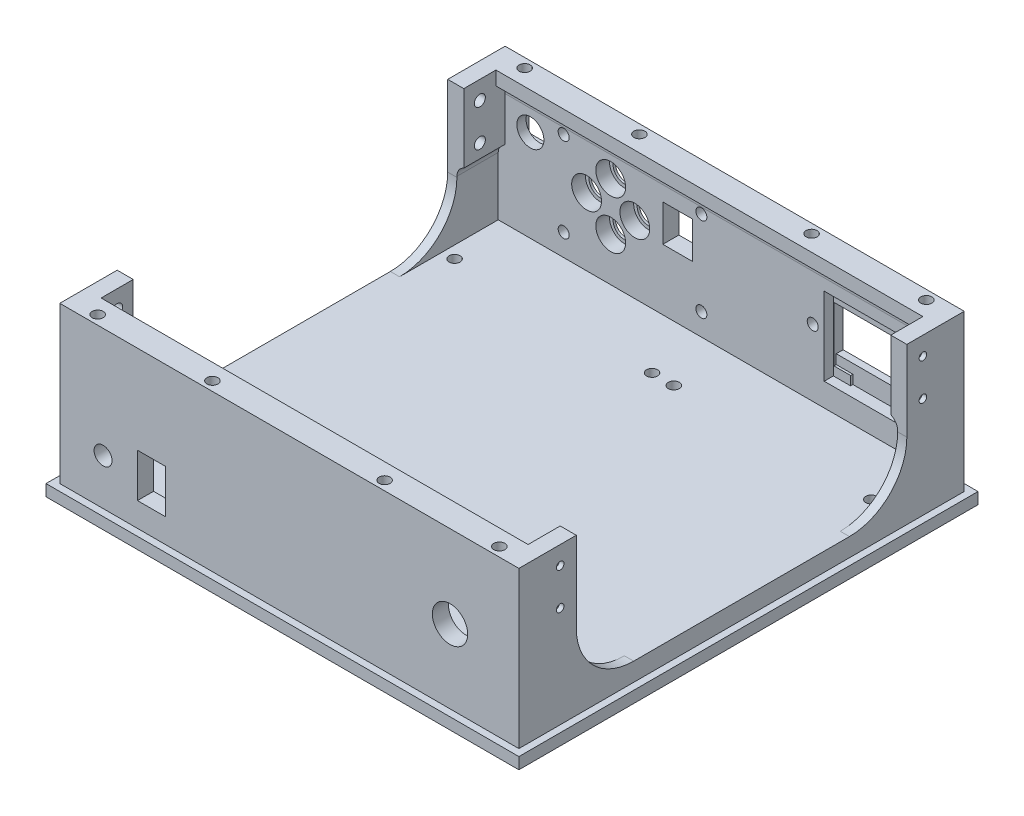
SolidWorks part; units mm, degrees
ref_plane "Front Plane" through (0, 0, 0) normal (0, 0, 1) x (1, 0, 0)
ref_plane "Top Plane" through (0, 0, 0) normal (0, 1, 0) x (1, 0, 0)
ref_plane "Right Plane" through (0, 0, 0) normal (1, 0, 0) x (0, 0, -1)
sketch "Sketch1" plane through (0, 0, 0) normal (0, 1, 0) x (1, 0, 0)
  line L1 (0, 0) -> (200, 0)
  line L2 (0, 0) -> (0, -194)
  line L3 (0, -194) -> (200, -194)
  line L4 (200, 0) -> (200, -194)
  dimension "D1" = 194
  dimension "D2" = 200
extrude "Boss-Extrude1" add sketch "Sketch1" along normal blind 8
sketch "Sketch4" plane through (0, 8, 0) normal (0, 1, 0) x (1, 0, 0)
  line L0 (0, -97) -> (200, -97) construction
  line L1 (0, 0) -> (0, -194) construction
  line L2 (200, -194) -> (200, 0) construction
  line L3 (100, 0) -> (100, -194) construction
  line L4 (200, 0) -> (0, 0) construction
  line L5 (0, -194) -> (200, -194) construction
  line L7 (9.25, -31.25) -> (95.25, -31.25) construction
  line L8 (9.25, -162.75) -> (95.25, -162.75) construction
  line L11 (190.75, -162.75) -> (104.75, -162.75) construction
  line L12 (190.75, -31.25) -> (104.75, -31.25) construction
  circle A0 centre (9.25, -31.25) radius 1.5 construction
  circle A1 centre (9.25, -31.25) radius 2.4
  circle A2 centre (95.25, -31.25) radius 1.5 construction
  circle A3 centre (95.25, -31.25) radius 2.4
  circle A4 centre (95.25, -162.75) radius 2.4
  circle A5 centre (95.25, -162.75) radius 1.5 construction
  circle A6 centre (9.25, -162.75) radius 2.4
  circle A7 centre (9.25, -162.75) radius 1.5 construction
  circle A8 centre (190.75, -162.75) radius 1.5 construction
  circle A9 centre (190.75, -162.75) radius 2.4
  circle A10 centre (104.75, -162.75) radius 1.5 construction
  circle A11 centre (104.75, -162.75) radius 2.4
  circle A12 centre (104.75, -31.25) radius 2.4
  circle A13 centre (104.75, -31.25) radius 1.5 construction
  circle A14 centre (190.75, -31.25) radius 2.4
  circle A15 centre (190.75, -31.25) radius 1.5 construction
  point P16 (9.25, -29.75)
  point P20 (7.75, -31.25)
  point P21 (96.75, -31.25)
  point P29 (96.75, -162.75)
  point P30 (7.75, -162.75)
  point P31 (9.25, -164.25)
  point P46 (190.75, -164.25)
  point P47 (192.25, -162.75)
  point P48 (103.25, -162.75)
  point P49 (103.25, -31.25)
  point P50 (192.25, -31.25)
  point P51 (190.75, -29.75)
  dimension "D1" = 3
  dimension "D2" = 4.8
  dimension "D4" = 3
  dimension "D5" = 4.8
  dimension "D3" = 67.25
  dimension "D6" = 89
  dimension "D7" = 4.75
  dimension "D8" = 9.5
  dimension "D9" = 134.5
  dimension "D10" = 184.5
extrude "Cut-Extrude1" cut sketch "Sketch4" against normal blind 6
sketch "Sketch5" plane through (0, 8, 0) normal (0, 1, 0) x (1, 0, 0)
  line L1 (0, 0) -> (200, 0)
  line L2 (0, 0) -> (0, -194)
  line L3 (0, -194) -> (200, -194)
  line L4 (200, 0) -> (200, -194)
  line L5 (196, -7) -> (196, -187)
  line L7 (4, -7) -> (4, -187)
  line L8 (196, -4) -> (196, -190) construction
  line L9 (4, -7) -> (196, -7)
  line L10 (4, -4) -> (4, -190) construction
  line L11 (4, -4) -> (196, -4) construction
  line L12 (0, -194) -> (0, -187) construction
  line L13 (4, -187) -> (196, -187)
  line L15 (4, -190) -> (196, -190) construction
  dimension "D1" = 4
  dimension "D2" = 7
extrude "Boss-Extrude4" add sketch "Sketch5" along normal blind 60
sketch "Sketch6" plane through (0, 0, 7) normal (0, 0, 1) x (1, 0, 0)
  line L7 (196, 68) -> (4, 68)
  line L8 (0, 68) -> (200, 68) construction
  line L9 (4, 68) -> (4, 62)
  line L11 (196, 62) -> (196, 68)
  line L12 (4, 62) -> (196, 62) construction
  line L13 (4, 62) -> (196, 62)
  dimension "D1" = 6
extrude "Boss-Extrude5" add sketch "Sketch6" along normal blind 4
sketch "Sketch7" plane through (0, 68, 0) normal (0, 1, 0) x (1, 0, 0)
  line L0 (0, 0) -> (0, -8) construction
  line L1 (0, 0) -> (0, -194) construction
  line L2 (0, -8) -> (200, -8) construction
  line L4 (200, -8) -> (200, 0) construction
  line L5 (200, 0) -> (0, 0) construction
  line L6 (0, -4) -> (200, -4) construction
  circle A0 centre (12.5, -4) radius 2.4
  circle A1 centre (62.5, -4) radius 2.4
  circle A2 centre (187.5, -4) radius 2.4
  circle A3 centre (137.5, -4) radius 2.4
  dimension "D2" = 4.8
  dimension "D3" = 4.8
  dimension "D4" = 4.8
  dimension "D5" = 4.8
  dimension "D1" = 8
  dimension "D6" = 12.5
  dimension "D7" = 50
  dimension "D8" = 12.5
  dimension "D9" = 50
extrude "Cut-Extrude2" cut sketch "Sketch7" against normal blind 6
ref_plane "Plane1" through (0, 0, 97) normal (0, 0, 1) x (1, 0, 0)
mirror "Mirror3" about plane through (0, 0, 97) normal (0, 0, 1) of "Boss-Extrude5"
mirror "Mirror5" about plane through (0, 0, 97) normal (0, 0, 1) of "Cut-Extrude2"
sketch "Sketch10" plane through (0, 0, 194) normal (0, 0, 1) x (1, 0, 0)
  line L0 (0, 68) -> (40, 68) construction
  line L1 (0, 68) -> (200, 68) construction
  line L2 (33.85, 20) -> (18.85, 20) construction
  line L3 (170, 0) -> (200, 0) construction
  line L4 (170, 32) -> (170, 0) construction
  line L5 (33.85, 29.5) -> (46.15, 29.5)
  line L6 (33.85, 29.5) -> (33.85, 10.5)
  line L7 (33.85, 10.5) -> (46.15, 10.5)
  line L8 (46.15, 29.5) -> (46.15, 10.5)
  line L9 (33.85, 29.5) -> (46.15, 10.5) construction
  line L10 (33.85, 10.5) -> (46.15, 29.5) construction
  line L11 (0, 0) -> (200, 0) construction
  line L12 (18.85, 20) -> (18.85, 0) construction
  circle A1 centre (18.85, 20) radius 3.9
  circle A3 centre (170, 32) radius 7.7
  point P8 (40, 20)
  point P22 (170, 32)
  point P24 (170, 0)
  dimension "D6" = 15.4
  dimension "7.8" = 7.8
  dimension "D8" = 32
  dimension "D1" = 40
  dimension "D2" = 19
  dimension "D3" = 12.3
  dimension "D4" = 20
  dimension "D5" = 15
  dimension "D7" = 30
extrude "Cut-Extrude4" cut sketch "Sketch10" against normal blind 10
ref_plane "Plane2" through (100, 0, 0) normal (1, 0, 0) x (0, 0, -1)
sketch "Sketch14" plane through (0, 0, 0) normal (0, 0, -1) x (-1, 0, 0)
  line L0 (0, 68) -> (-15, 68) construction
  line L1 (-200, 68) -> (0, 68) construction
  line L2 (-15, 68) -> (-15, 48) construction
  dimension "D1" = 15
  dimension "D2" = 20
sketch "Sketch16" plane through (0, 0, 0) normal (0, 0, -1) x (-1, 0, 0)
  line L0 (-75.7, 50.6) -> (-75.7, 34.6)
  line L1 (-75.7, 34.6) -> (-88.7, 34.6)
  line L2 (-88.7, 34.6) -> (-88.7, 50.6)
  line L3 (-88.7, 50.6) -> (-75.7, 50.6)
  line L4 (-75.7, 34.6) -> (-63.5, 34.6) construction
  line L5 (-63.5, 34.6) -> (-63.5, 37.5) construction
  line L6 (-63.5, 37.5) -> (-42.5, 37.5) construction
  line L7 (-53, 48) -> (-53, 27) construction
  line L8 (-18, 48) -> (-18, 37.5) construction
  line L9 (-18, 37.5) -> (-42.5, 37.5) construction
  line L11 (-18, 48) -> (0, 48) construction
  line L12 (0, 68) -> (0, 0) construction
  circle A0 centre (-53, 48) radius 5
  circle A1 centre (-63.5, 37.5) radius 5
  circle A2 centre (-42.5, 37.5) radius 5
  circle A3 centre (-53, 27) radius 5
  circle A4 centre (-18, 48) radius 5.9
  dimension "D5" = 10
  dimension "D6" = 10
  dimension "D7" = 10
  dimension "D8" = 10
  dimension "D13" = 11.8
  dimension "D1" = 12.2
  dimension "D2" = 16
  dimension "D3" = 13
  dimension "D4" = 2.9
  dimension "D9" = 21
  dimension "D10" = 21
  dimension "D11" = 24.5
  dimension "D12" = 10.5
  dimension "D14" = 14.8492
  dimension "D15" = 14.8492
  dimension "D16" = 18
extrude "Cut-Extrude5" cut sketch "Sketch16" against normal blind 10
sketch "Sketch17" plane through (0, 0, 0) normal (0, 0, -1) x (-1, 0, 0)
  line L1 (-25.5, 55.5) -> (-10.5, 55.5)
  line L2 (-25.5, 55.5) -> (-25.5, 40.5)
  line L3 (-25.5, 40.5) -> (-10.5, 40.5)
  line L4 (-10.5, 55.5) -> (-10.5, 40.5)
  line L5 (-25.5, 55.5) -> (-10.5, 40.5) construction
  line L6 (-25.5, 40.5) -> (-10.5, 55.5) construction
  point P0 (-18, 48)
  dimension "D1" = 15
extrude "Cut-Extrude6" cut sketch "Sketch17" against normal blind 3
sketch "Sketch19" plane through (0, 0, 7) normal (0, 0, 1) x (1, 0, 0)
  line L0 (32.5, 54.4) -> (92.5, 54.4) construction
  line L1 (92.5, 54.4) -> (92.5, 17.6) construction
  line L2 (92.5, 17.6) -> (32.5, 17.6) construction
  line L3 (32.5, 17.6) -> (32.5, 54.4) construction
  line L4 (42.5, 37.5) -> (32.5, 37.5) construction
  circle A0 centre (32.5, 54.4) radius 2.4
  circle A1 centre (92.5, 54.4) radius 2.4
  circle A2 centre (92.5, 17.6) radius 2.4
  circle A3 centre (32.5, 17.6) radius 2.4
  circle A6 centre (42.5, 37.5) radius 5
  circle A7 centre (42.5, 37.5) radius 5 construction
  point P12 (42.5, 37.5)
  dimension "D7" = 4.8
  dimension "D8" = 4.8
  dimension "D9" = 4.8
  dimension "D10" = 4.8
  dimension "D1" = 36.8
  dimension "D2" = 10
  dimension "D4" = 60
  dimension "D5" = 60
  dimension "D6" = 36.8
  dimension "D11" = 0
extrude "Cut-Extrude7" cut sketch "Sketch19" against normal blind 5
sketch "Sketch20" plane through (0, 0, 7) normal (0, 0, 1) x (1, 0, 0)
  circle A0 centre (53, 48) radius 6.5
  circle A1 centre (42.5, 37.5) radius 6.5
  circle A2 centre (53, 27) radius 6.5
  circle A3 centre (63.5, 37.5) radius 6.5
  dimension "D1" = 13
  dimension "D2" = 13
  dimension "D3" = 13
  dimension "D4" = 13
extrude "Cut-Extrude8" cut sketch "Sketch20" against normal blind 6
sketch "Sketch22" plane through (0, 0, 7) normal (0, 0, 1) x (1, 0, 0)
  line L0 (181, 52.101) -> (181, 62) construction
  line L2 (4, 62) -> (196, 62) construction
  line L3 (146, 52.101) -> (181, 52.101)
  line L4 (146, 18.101) -> (181, 18.101)
  line L5 (181, 18.101) -> (181, 52.101)
  line L6 (146, 52.101) -> (146, 18.101)
  line L7 (146.25, 46.001) -> (180.75, 46.001) construction
  line L8 (180.75, 46.001) -> (180.75, 26.101) construction
  line L9 (180.75, 26.101) -> (146.25, 26.101) construction
  line L10 (146.25, 26.101) -> (146.25, 46.001) construction
  line L11 (146.25, 26.101) -> (146.25, 22.001) construction
  line L12 (146.25, 22.001) -> (153.5, 22.001) construction
  line L13 (153.5, 22.001) -> (153.5, 18.101) construction
  line L14 (180.75, 26.101) -> (180.75, 22.001) construction
  line L15 (180.75, 22.001) -> (173.5, 22.001) construction
  line L16 (173.5, 22.001) -> (173.5, 18.101) construction
  line L17 (181, 62) -> (196, 62) construction
  dimension "D3" = 35
  dimension "D4" = 34.5
  dimension "D5" = 34
  dimension "D6" = 34
  dimension "D7" = 35
  dimension "D8" = 3.9
  dimension "D9" = 7.25
  dimension "D10" = 3.9
  dimension "D11" = 7.25
  dimension "D12" = 34.5
  dimension "D13" = 19.9
  dimension "D14" = 34.5
  dimension "D15" = 19.9
  dimension "D16" = 4.1
  dimension "D17" = 4.1
extrude "Cut-Extrude9" cut sketch "Sketch22" against normal blind 4
sketch "Sketch23" plane through (0, 0, 3) normal (0, 0, 1) x (1, 0, 0)
  line L0 (146.25, 46.001) -> (180.75, 46.001)
  line L1 (180.75, 46.001) -> (180.75, 26.101)
  line L2 (180.75, 26.101) -> (146.25, 26.101)
  line L3 (146.25, 26.101) -> (146.25, 46.001)
extrude "Cut-Extrude10" cut sketch "Sketch23" against normal blind 12
sketch "Sketch24" plane through (0, 0, 3) normal (0, 0, 1) x (1, 0, 0)
  line L0 (146.25, 26.101) -> (146.25, 22.001)
  line L1 (146.25, 22.001) -> (153.5, 22.001)
  line L2 (153.5, 22.001) -> (153.5, 18.101)
  line L3 (153.5, 18.101) -> (173.5, 18.101)
  line L4 (173.5, 18.101) -> (173.5, 22.001)
  line L5 (173.5, 22.001) -> (180.75, 22.001)
  line L6 (180.75, 22.001) -> (180.75, 26.101)
  line L7 (180.75, 26.101) -> (146.25, 26.101)
extrude "Cut-Extrude11" cut sketch "Sketch24" against normal blind 1
sketch "Sketch25" plane through (0, 0, 7) normal (0, 0, 1) x (1, 0, 0)
  line L0 (181, 52.101) -> (181, 18.101) construction
  line L1 (146, 52.101) -> (146, 18.101) construction
  line L2 (146, 37.101) -> (181, 37.101) construction
  line L3 (181, 37.101) -> (181, 52.101) construction
  line L4 (146, 37.101) -> (141, 37.101) construction
  line L5 (181, 37.101) -> (186, 37.101) construction
  circle A0 centre (141, 37.101) radius 2.4
  circle A1 centre (186, 37.101) radius 2.4
  point P8 (146, 37.101)
  dimension "D4" = 4.8
  dimension "D5" = 4.8
  dimension "D1" = 15
  dimension "D2" = 5
  dimension "D3" = 5
extrude "Cut-Extrude12" cut sketch "Sketch25" against normal blind 5
sketch "Sketch26" plane through (0, 0, 0) normal (-1, 0, 0) x (0, 0, 1)
  line L0 (0, 68) -> (25, 68) construction
  line L1 (0, 68) -> (194, 68) construction
  line L2 (194, 68) -> (169, 68) construction
  line L3 (25, 68) -> (169, 68)
  line L4 (169, 68) -> (169, 8)
  line L5 (169, 8) -> (25, 8)
  line L6 (25, 8) -> (25, 68)
  dimension "D1" = 25
  dimension "D2" = 25
  dimension "D3" = 60
extrude "Cut-Extrude13" cut sketch "Sketch26" against normal through all
sketch "Sketch27" plane through (0, 0, 0) normal (0, 0, -1) x (-1, 0, 0)
  line L10 (-184.75, 22.101) -> (-142.25, 22.101)
  line L11 (-142.25, 22.101) -> (-142.25, 50.001)
  line L12 (-142.25, 50.001) -> (-184.75, 50.001)
  line L13 (-184.75, 50.001) -> (-184.75, 22.101)
  line L14 (-146.25, 26.101) -> (-146.25, 46.001)
  line L15 (-180.75, 26.101) -> (-146.25, 26.101)
  line L16 (-180.75, 46.001) -> (-180.75, 26.101)
  line L17 (-146.25, 46.001) -> (-180.75, 46.001)
  line L18 (-146.25, 26.101) -> (-146.25, 46.001)
  line L19 (-180.75, 26.101) -> (-146.25, 26.101)
  line L20 (-180.75, 46.001) -> (-180.75, 26.101)
  line L21 (-146.25, 46.001) -> (-180.75, 46.001)
  dimension "D1" = 0
  dimension "D2" = 4
extrude "Boss-Extrude7" add sketch "Sketch27" along normal blind 1
fillet "Fillet5" radius 5 4 edges at (142.25, 50.001, -0.5) (142.25, 22.101, -0.5) (184.75, 22.101, -0.5) (184.75, 50.001, -0.5)
sketch "Sketch28" plane through (196, 0, 0) normal (-1, 0, 0) x (0, 0, 1)
  line L0 (25, 68) -> (11, 68)
  line L1 (11, 68) -> (11, 62)
  line L2 (11, 38) -> (25, 38)
  line L4 (25, 38) -> (25, 68)
  line L5 (183, 68) -> (169, 68)
  line L6 (169, 68) -> (169, 38)
  line L8 (169, 38) -> (183, 38)
  line L9 (183, 62) -> (183, 68)
  line L10 (11, 62) -> (7, 62)
  line L11 (11, 62) -> (7, 62) construction
  line L12 (7, 62) -> (7, 8) construction
  line L13 (7, 62) -> (7, 38)
  line L14 (7, 38) -> (11, 38)
  line L15 (183, 62) -> (187, 62)
  line L16 (187, 62) -> (187, 38)
  line L17 (187, 62) -> (187, 8) construction
  line L18 (187, 38) -> (183, 38)
  dimension "D1" = 30
  dimension "D2" = 30
extrude "Boss-Extrude8" add sketch "Sketch28" along normal blind 3
fillet "Fillet6" radius 5 2 edges at (196, 38, 178) (196, 38, 16)
sketch "Sketch30" plane through (193, 0, 0) normal (-1, 0, 0) x (0, 0, 1)
  line L0 (0, 68) -> (18, 68) construction
  line L1 (25, 68) -> (11, 68) construction
  line L2 (18, 68) -> (18, 60) construction
  line L3 (18, 60) -> (18, 52) construction
  line L4 (18, 52) -> (18, 44) construction
  line L5 (97, 0) -> (97, 74.9395) construction
  line L6 (194, 0) -> (0, 0) construction
  line L7 (97, -40.15) -> (97, 40.15) construction
  circle A0 centre (18, 60) radius 2.4
  circle A2 centre (18, 44) radius 2.4
  circle A3 centre (176, 44) radius 2.4
  circle A5 centre (176, 60) radius 2.4
  dimension "D5" = 4.8
  dimension "D7" = 4.8
  dimension "D1" = 8
  dimension "D2" = 8
  dimension "D3" = 8
  dimension "D4" = 18
extrude "Cut-Extrude14" cut sketch "Sketch30" against normal blind 5
sketch "Sketch32" plane through (198, 0, 0) normal (-1, 0, 0) x (0, 0, 1)
  line L0 (97, -40.15) -> (97, 40.15) construction
  circle A1 centre (18, 60) radius 1.65
  circle A2 centre (18, 44) radius 1.65
  circle A4 centre (176, 44) radius 1.65
  circle A6 centre (176, 60) radius 1.65
  dimension "D2" = 3.3
  dimension "D3" = 3.3
extrude "Cut-Extrude15" cut sketch "Sketch32" against normal blind 15
mirror "Mirror8" about plane through (100, 0, 0) normal (1, 0, 0) of "Cut-Extrude15", "Cut-Extrude14", "Boss-Extrude8"
fillet "Fillet7" radius 5 2 edges at (4, 38, 178) (4, 38, 16)
fillet "Fillet8" radius 5 1 edges at (100, 62, 7)
fillet "Fillet9" radius 5 1 edges at (100, 62, 187)
fillet "Fillet10" radius 25 4 edges at (198, 8, 25) (198, 8, 169) (2, 8, 169) (2, 8, 25)
sketch "Sketch33" plane through (0, 0, 0) normal (0, -1, 0) x (1, 0, 0)
  line L9 (0, 194) -> (0, 0) construction
  line L10 (0, 0) -> (200, 0) construction
  line L11 (200, 0) -> (200, 194) construction
  line L12 (200, 194) -> (0, 194) construction
  line L13 (0, 194) -> (-3, 194) construction
  line L14 (0, 194) -> (0, 197) construction
  line L15 (-3, 194) -> (-3, 197) construction
  line L16 (-3, 197) -> (0, 197) construction
  line L17 (-3, 197) -> (203, 197)
  line L18 (203, 197) -> (203, -3)
  line L19 (203, -3) -> (-3, -3)
  line L20 (-3, -3) -> (-3, 197)
  dimension "D1" = 3
  dimension "D2" = 3
  dimension "D3" = 206
  dimension "D4" = 200
extrude "Boss-Extrude9" add sketch "Sketch33" along normal blind 5
sketch "Sketch34" plane through (0, 0, 7) normal (0, 0, 1) x (1, 0, 0)
  line L0 (141, 37.101) -> (186, 37.101) construction
